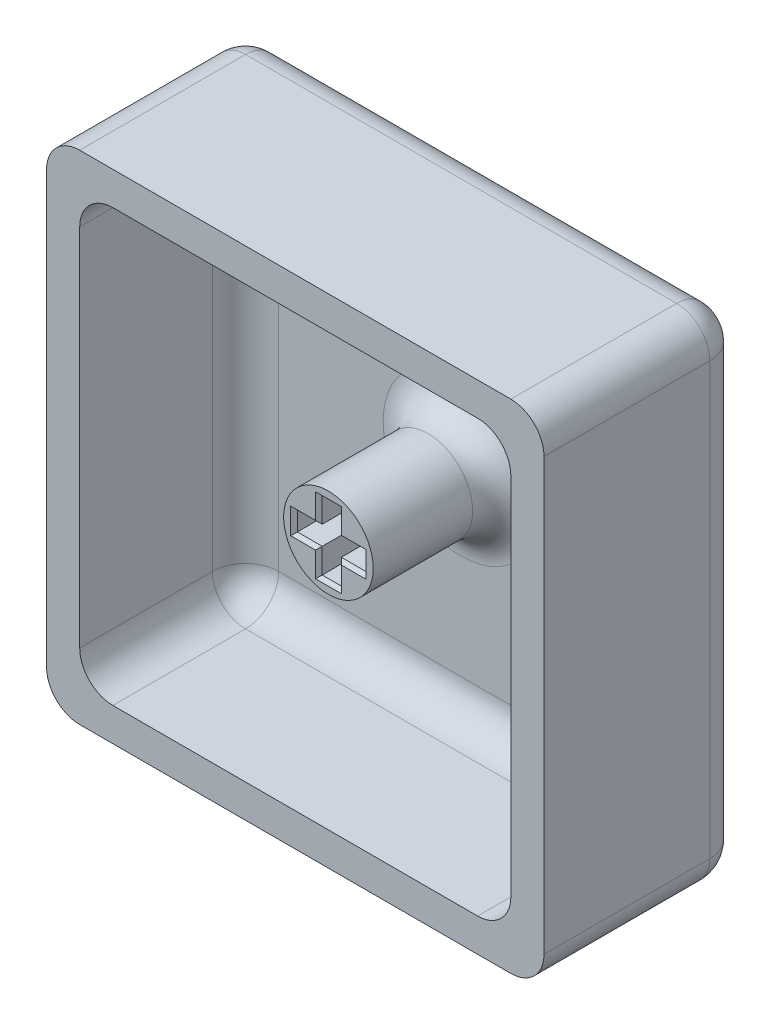
SolidWorks part; units mm, degrees
ref_plane "前视基准面" through (0, 0, 0) normal (0, 0, 1) x (1, 0, 0)
ref_plane "上视基准面" through (0, 0, 0) normal (0, 1, 0) x (1, 0, 0)
ref_plane "右视基准面" through (0, 0, 0) normal (1, 0, 0) x (0, 0, -1)
sketch "草图1" plane through (0, 0, 0) normal (0, 0, 1) x (1, 0, 0)
  line L0 (-13, 15) -> (13, 15)
  line L1 (-11, 13) -> (11, 13)
  line L2 (-13, 11) -> (-13, -11)
  line L3 (-11, -13) -> (11, -13)
  line L4 (13, 11) -> (13, -11)
  line L5 (0, -13) -> (0, 13) construction
  line L6 (-13, 0) -> (13, 0) construction
  line L7 (15, 13) -> (15, -13)
  line L8 (-13, -15) -> (13, -15)
  line L9 (-15, 13) -> (-15, -13)
  line L10 (-13, -13) -> (13, -13) construction
  line L11 (-2.075, 0.575) -> (2.075, 0.575)
  line L12 (-2.075, 0.575) -> (-2.075, -0.575)
  line L13 (-2.075, -0.575) -> (2.075, -0.575)
  line L14 (2.075, 0.575) -> (2.075, -0.575)
  line L15 (0, -0.575) -> (0, 0.575) construction
  line L16 (-2.075, 0) -> (2.075, 0) construction
  line L17 (-0.575, 2.075) -> (0.575, 2.075)
  line L18 (-0.575, 2.075) -> (-0.575, -2.075)
  line L19 (-0.575, -2.075) -> (0.575, -2.075)
  line L20 (0.575, 2.075) -> (0.575, -2.075)
  line L21 (0, -2.075) -> (0, 2.075) construction
  line L22 (-0.575, 0) -> (0.575, 0) construction
  line L23 (13, 13) -> (13, -13) construction
  line L24 (-13, 13) -> (13, 13) construction
  line L25 (-13, 13) -> (-13, -13) construction
  line L26 (-15, 15) -> (-15, -15) construction
  line L27 (-15, -15) -> (15, -15) construction
  line L28 (15, 15) -> (15, -15) construction
  line L29 (-15, 15) -> (15, 15) construction
  line L36 (-13, 0) -> (-2.5, 0) construction
  circle A0 centre (0, 0) radius 2.7
  arc A1 (11, -13) -> (13, -11) centre (11, -11) ccw
  arc A2 (13, 11) -> (11, 13) centre (11, 11) ccw
  arc A3 (-13, 11) -> (-11, 13) centre (-11, 11) cw
  arc A4 (-13, -11) -> (-11, -13) centre (-11, -11) ccw
  arc A5 (-15, -13) -> (-13, -15) centre (-13, -13) ccw
  arc A6 (13, -15) -> (15, -13) centre (13, -13) ccw
  arc A7 (15, 13) -> (13, 15) centre (13, 13) ccw
  arc A8 (-15, 13) -> (-13, 15) centre (-13, 13) cw
  point P0 (0, 0)
  point P19 (13, -13)
  point P66 (0.0162, 0.0162)
  dimension "D4" = 5.4
  dimension "D9" = 2
  dimension "D1" = 30
  dimension "D2" = 30
  dimension "D5" = 4.15
  dimension "D6" = 1.15
  dimension "D7" = 4.15
  dimension "D8" = 1.15
  dimension "D3" = 2
extrude "凸台-拉伸1" add sketch "草图1" along normal blind 10 contours A8 L9 A5 L8 A6 L7 A7 L0 A4 L2 A3 L1 A2 L4 A1 L3 region at (0, 14.5757, 0)
extrude "凸台-拉伸2" add sketch "草图1<6>" along normal blind 8 separate body contours A0 L17 L20 L11 L14 L13 L19 L18 L12 region at (-2.6236, 0, 0)
sketch "草图1<6>" plane through (0, 0, 0) normal (0, 0, 1) x (1, 0, 0) same geometry as "草图1"
extrude "凸台-拉伸3" add sketch "草图1<7>" against normal blind 2 contours L8 A6 L7 A7 L0 A8 L9 A5
sketch "草图1<7>" plane through (0, 0, 0) normal (0, 0, 1) x (1, 0, 0) same geometry as "草图1"
fillet "圆角1" radius 2 8 edges at (-14.4142, 14.4142, -2) (-15, 0, -2) (-14.4142, -14.4142, -2) (0, -15, -2) (14.4142, -14.4142, -2) (15, 0, -2) (14.4142, 14.4142, -2) (0, 15, -2)
fillet "圆角5" radius 2 9 edges at (-12.4142, 12.4142, 0) (0, 13, 0) (12.4142, 12.4142, 0) (13, 0, 0) (12.4142, -12.4142, 0) (0, -13, 0) (-12.4142, -12.4142, 0) (-13, 0, 0) (2.7, 0, 0)
chamfer "倒角1" distance 0.2 angle 45 12 edges at (-0.575, 1.325, 8) (-1.325, 0.575, 8) (-2.075, 0, 8) (-1.325, -0.575, 8) (-0.575, -1.325, 8) (0, -2.075, 8) (0.575, -1.325, 8) (1.325, -0.575, 8) (2.075, 0, 8) (1.325, 0.575, 8) (0.575, 1.325, 8) (0, 2.075, 8)
